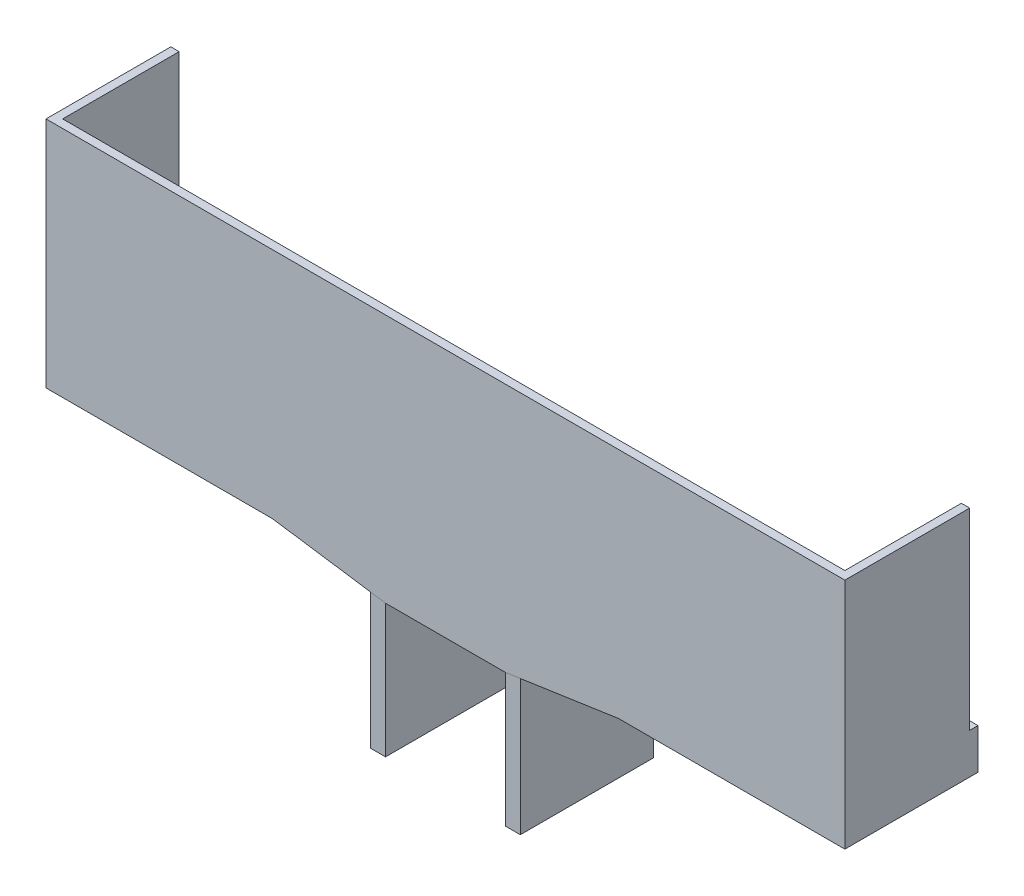
SolidWorks part; units mm, degrees
ref_plane "前基準面" through (0, 0, 0) normal (0, 0, 1) x (1, 0, 0)
ref_plane "上基準面" through (0, 0, 0) normal (0, 1, 0) x (1, 0, 0)
ref_plane "右基準面" through (0, 0, 0) normal (1, 0, 0) x (0, 0, -1)
sketch "草圖20" plane through (0, 0, 0) normal (0, 0, 1) x (1, 0, 0)
  line L0 (-36, 0) -> (36, 0) construction
  line L1 (-36, 0) -> (-240, 30)
  line L2 (-240, 30) -> (240, 30) construction
  line L3 (240, 30) -> (36, 0)
  line L4 (36, 0) -> (-36, 0)
  line L5 (0, 89.4424) -> (0, -40.7257) construction
  line L7 (-240, 30) -> (240, 30) construction
  line L8 (-240, 30) -> (-240, 150)
  line L9 (-240, 150) -> (240, 150)
  line L10 (240, 30) -> (240, 150)
  point P2 (0, 0)
  dimension "D1" = 72
  dimension "D2" = 480
  dimension "D3" = 30
  dimension "D4" = 120
extrude "填料-伸長1" add sketch "草圖20" along normal blind 80
ref_plane "平面1" through (0, 0, 5) normal (0, 0, 1) x (1, 0, 0)
sketch "草圖22" plane through (0, 0, 5) normal (0, 0, 1) x (1, 0, 0)
  line L6 (-235, 34.3185) -> (-35.6343, 5)
  line L7 (-235, 34.3185) -> (-36, 5.0538)
  line L8 (35.6343, 5) -> (235, 34.3185)
  line L9 (36, 5.0538) -> (235, 34.3185)
  line L332 (36, 0) -> (36, 5.0538)
  line L333 (-36, 0) -> (-36, 5.0538)
  line L334 (-36, 0) -> (36, 0) construction
  line L335 (-36, 0) -> (36, 0)
  line L336 (240, 150) -> (-240, 150) construction
  line L337 (235, 150) -> (-235, 150)
  line L338 (-35.6343, 5) -> (35.6343, 5)
  line L340 (-235, 145) -> (-235, 34.3185)
  line L341 (235, 145) -> (-235, 145)
  line L342 (235, 34.3185) -> (235, 145)
  line L346 (-235, 150) -> (-235, 34.3185)
  line L348 (235, 34.3185) -> (235, 150)
  dimension "D1" = 5
extrude "除料-伸長1" cut sketch "草圖22" along normal blind 70
sketch "草圖23" plane through (0, 0, 0) normal (0, 0, -1) x (-1, 0, 0)
  line L0 (-240, 34.3185) -> (240, 34.3185)
  line L1 (-240, 150) -> (240, 150)
  line L2 (-240, 150) -> (-240, 34.3185)
  line L4 (240, 150) -> (240, 34.3185)
  line L5 (240, 150) -> (240, 30) construction
  line L15 (-36, 0) -> (36, 0)
  line L16 (-36, 5.0538) -> (-36, 0)
  line L17 (-235, 34.3185) -> (-36, 5.0538)
  line L18 (-235, 150) -> (-235, 34.3185)
  line L19 (235, 150) -> (-235, 150)
  line L20 (235, 34.3185) -> (235, 150)
  line L21 (36, 5.0538) -> (235, 34.3185)
  line L22 (36, 0) -> (36, 5.0538)
  line L23 (-36, 0) -> (36, 0) construction
  line L24 (-36, 5.0538) -> (-36, 0) construction
  line L25 (-235, 34.3185) -> (-36, 5.0538) construction
  line L26 (-235, 150) -> (-235, 34.3185) construction
  line L27 (235, 150) -> (-235, 150) construction
  line L28 (235, 34.3185) -> (235, 150) construction
  line L29 (36, 5.0538) -> (235, 34.3185) construction
  line L30 (36, 0) -> (36, 5.0538) construction
  dimension "D1" = 0
extrude "除料-伸長2" cut sketch "草圖23" against normal up to surface (5 mm away) up to face at (0, 47.3431, 5)
sketch "草圖25" plane through (0, 0, 0) normal (0, -1, 0) x (1, 0, 0)
  line L0 (-240, 80) -> (-36, 80) construction
  line L1 (-45, 80) -> (-36, 80)
  line L2 (-45, 80) -> (-45, 0)
  line L3 (-45, 0) -> (-36, 0)
  line L4 (45, 80) -> (45, 0)
  line L5 (36, 0) -> (240, 0) construction
  line L8 (-36, 75) -> (-36, 5) construction
  line L9 (-36, 75) -> (-36, 5)
  line L10 (36, 75) -> (36, 5) construction
  line L11 (36, 75) -> (36, 5)
  line L14 (0, 112.0403) -> (0, -32.5908) construction
  line L15 (-36, 80) -> (-36, 0)
  line L16 (36, 80) -> (45, 80)
  line L17 (36, 80) -> (36, 0)
  line L18 (36, 0) -> (45, 0)
  line M10 (-36, 80) -> (-36, 75)
  line M12 (36, 75) -> (36, 80)
  dimension "D1" = 90
extrude "填料-伸長3" add sketch "草圖25" along normal blind 80 and the other way up to next separate body contours L15 L9 L1 L2 L3 M10 | L17 L18 L4 L16 L11 M12 region at (-40.5, 0, 40) region at (40.5, 0, 40)
sketch "草圖26" plane through (0, 0, 0) normal (0, 0, -1) x (-1, 0, 0)
  line L0 (-104, 10) -> (-240, 10)
  line L1 (-36, 0) -> (-240, 30) construction
  line L2 (-240, 10) -> (-240, 30)
  line L3 (-240, 30) -> (-104, 10)
  line L4 (36, 0) -> (-36, 0) construction
  line L5 (0, 209.7105) -> (0, -36.6515) construction
  line L6 (240, 10) -> (240, 30)
  line L7 (104, 10) -> (240, 10)
  line L8 (240, 30) -> (104, 10)
  dimension "D1" = 10
extrude "填料-伸長4" add sketch "草圖26" against normal up to surface (80 mm away) up to face at (0, 60, 80)
